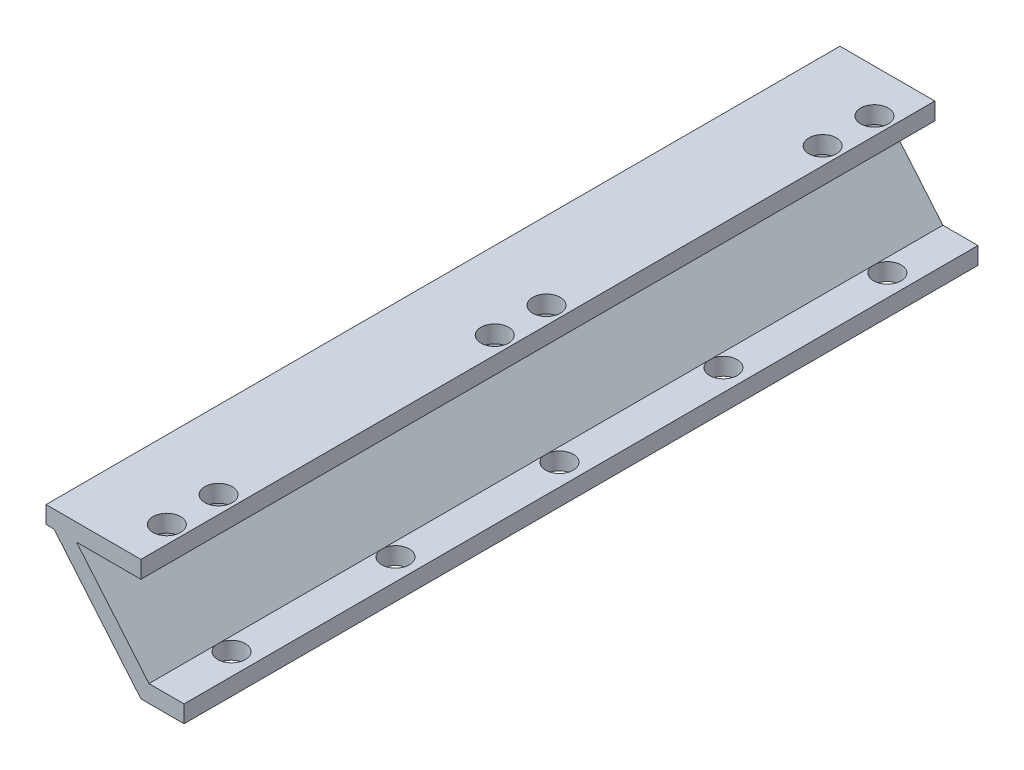
SolidWorks part; units mm, degrees
ref_plane "Front Plane" through (0, 0, 0) normal (0, 0, 1) x (1, 0, 0)
ref_plane "Top Plane" through (0, 0, 0) normal (0, 1, 0) x (1, 0, 0)
ref_plane "Right Plane" through (0, 0, 0) normal (1, 0, 0) x (0, 0, -1)
sketch "스케치1" plane through (0, 0, 0) normal (0, 0, 1) x (1, 0, 0)
  line L0 (0, 0) -> (50000, 0) construction
  line L1 (0, 0) -> (0, 50000) construction
  line L2 (0, 0) -> (-32139.3805, 38302.2222) construction
  line L3 (-3.1135, 6.8219) -> (-32142.494, 38309.0441) construction
  line L4 (76.8945, 2) -> (-49923.1055, 2) construction
  line L5 (-34.4266, 12) -> (-50034.4266, 12) construction
  line L6 (-40.9601, 14) -> (-50040.9601, 14) construction
  line L7 (5, -3.8411) -> (5, 49996.1589) construction
  line L8 (-10.0692, 12) -> (-10.0692, 27.1958) construction
  line L9 (-11, 12) -> (-11, 15.0198) construction
  line L10 (5, 0) -> (0, 0)
  line L11 (0, 0) -> (-10.0692, 12)
  line L12 (-10.0692, 12) -> (-11, 12)
  line L13 (-11, 12) -> (-11, 14)
  line L14 (-11, 14) -> (0, 14)
  line L15 (0, 14) -> (0, 12)
  line L16 (0, 12) -> (-7.4584, 12)
  line L17 (-7.4584, 12) -> (0.9326, 2)
  line L18 (0.9326, 2) -> (5, 2)
  line L19 (5, 2) -> (5, 0)
  line L20 (11.7496, 17.5) -> (-49988.2504, 17.5) construction
  dimension "D1" = 2
  dimension "D2" = 50
  dimension "D3" = 2
  dimension "D4" = 2
  dimension "D5" = 12
  dimension "D6" = 5
  dimension "D7" = 11
  dimension "D8" = 3.5
extrude "보스-돌출1" add sketch "스케치1" against normal blind 46 and the other way blind 46
sketch "스케치2" plane through (0, 14, 0) normal (0, 1, 0) x (1, 0, 0)
  line L0 (-1000, 0) -> (49000, 0) construction
  line L1 (-999.0674, 38) -> (49000.9326, 38) construction
  line L3 (-999.0674, -38) -> (49000.9326, -38) construction
  line L5 (-1000, -41) -> (49000, -41) construction
  line L7 (-1001.0794, -35) -> (48998.9206, -35) construction
  line L8 (-1000, -3) -> (49000, -3) construction
  line L10 (-1001.2074, 3) -> (48998.7926, 3) construction
  line L11 (-1000.9513, 35) -> (48999.0487, 35) construction
  line L12 (-1001.9757, 41) -> (48998.0243, 41) construction
  line L13 (-2, -988.1885) -> (-2, 49011.8115) construction
  line L14 (0, -46) -> (0, 46) construction
  circle A0 centre (-2, 41) radius 1.6
  circle A1 centre (-2, 35) radius 1.6
  circle A2 centre (-2, 3) radius 1.6
  circle A3 centre (-2, -3) radius 1.6
  circle A4 centre (-2, -35) radius 1.6
  circle A5 centre (-2, -41) radius 1.6
  dimension "D1" = 38
  dimension "D2" = 38
  dimension "D3" = 3
  dimension "D4" = 3
  dimension "D5" = 3
  dimension "D6" = 3
  dimension "D7" = 3
  dimension "D8" = 3
  dimension "D9" = 2
extrude "컷-돌출1" cut sketch "스케치2" against normal blind 5
sketch "스케치3" plane through (0, 2, 0) normal (0, 1, 0) x (1, 0, 0)
  line L0 (0, 0) -> (50000, 0) construction
  line L1 (11.4689, 38) -> (50011.4689, 38) construction
  line L2 (14.2858, -38) -> (50014.2858, -38) construction
  line L3 (20.4319, -19) -> (50020.4319, -19) construction
  line L4 (26.9621, 19) -> (50026.9621, 19) construction
  line L5 (2.5, 25.6087) -> (2.5, -49974.3913) construction
  line L6 (5, -46) -> (5, 46) construction
  circle A0 centre (2.5, 38) radius 1.6
  circle A1 centre (2.5, 19) radius 1.6
  circle A2 centre (2.5, 0) radius 1.6
  circle A3 centre (2.5, -19) radius 1.6
  circle A4 centre (2.5, -38) radius 1.6
  dimension "D1" = 2.5
  dimension "D2" = 38
  dimension "D3" = 38
  dimension "D4" = 19
  dimension "D5" = 19
extrude "컷-돌출2" cut sketch "스케치3" against normal blind 5
